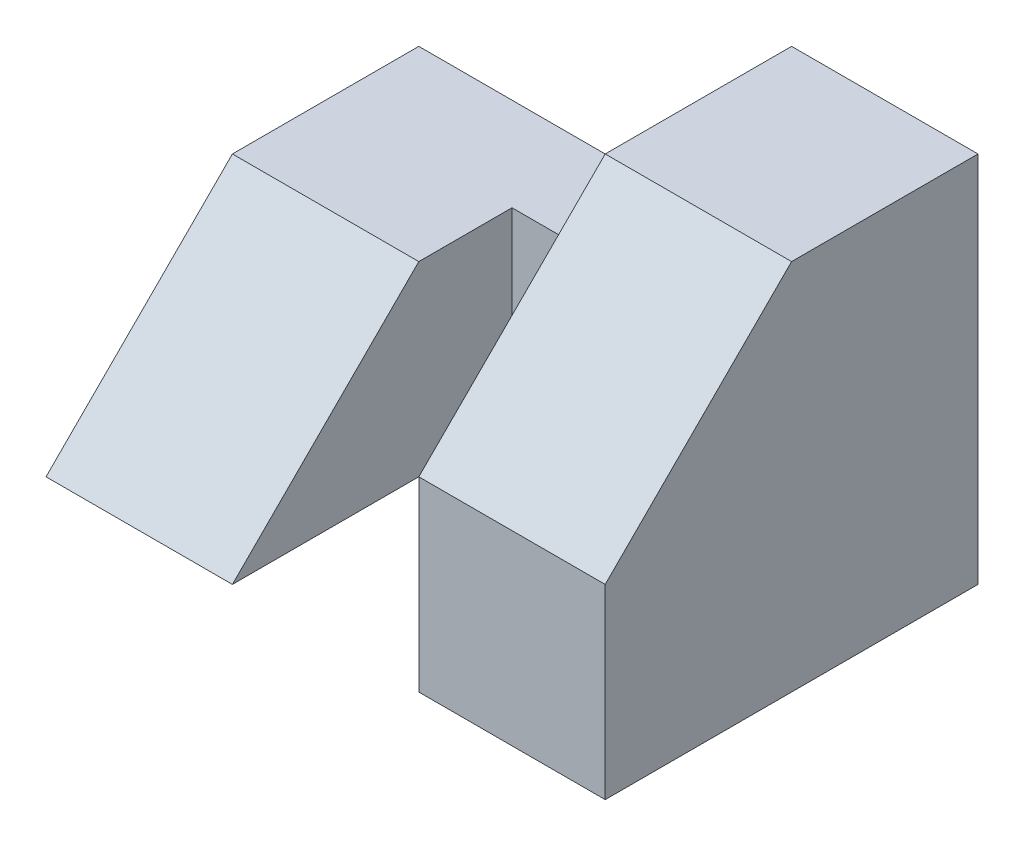
SolidWorks part; units mm, degrees
ref_plane "Front Plane" through (0, 0, 0) normal (0, 0, 1) x (1, 0, 0)
ref_plane "Top Plane" through (0, 0, 0) normal (0, 1, 0) x (1, 0, 0)
ref_plane "Right Plane" through (0, 0, 0) normal (1, 0, 0) x (0, 0, -1)
sketch "Sketch2" plane through (0, 0, 0) normal (0, 0, 1) x (1, 0, 0)
  line L1 (-76.2, -50.8) -> (76.2, -50.8)
  line L2 (-76.2, -50.8) -> (-76.2, 50.8)
  line L3 (-76.2, 50.8) -> (76.2, 50.8)
  line L4 (76.2, -50.8) -> (76.2, 50.8)
  line L5 (-76.2, -50.8) -> (76.2, 50.8) construction
  line L6 (-76.2, 50.8) -> (76.2, -50.8) construction
  point P0 (0, 0)
  dimension "D1" = 152.4
  dimension "D2" = 101.6
extrude "Boss-Extrude1" add sketch "Sketch2" along normal mid plane 101.6
sketch "Sketch4" plane through (0, 0, 50.8) normal (0, 0, 1) x (1, 0, 0)
  line L0 (76.2, -50.8) -> (76.2, 50.8) construction
  line L1 (-76.2, 50.8) -> (25.4, 50.8)
  line L2 (-76.2, 50.8) -> (-76.2, 0)
  line L3 (-76.2, 0) -> (25.4, 0)
  line L4 (25.4, 50.8) -> (25.4, 0)
  line L5 (-76.2, 50.8) -> (25.4, 0) construction
  line L6 (-76.2, 0) -> (25.4, 50.8) construction
  point P4 (-25.4, 25.4)
  dimension "D1" = 0
  dimension "D2" = 50.8
extrude "Cut-Extrude1" cut sketch "Sketch4" against normal through all
sketch "Sketch5" plane through (0, 0, 0) normal (0, 1, 0) x (1, 0, 0)
  line L0 (-76.2, 50.8) -> (25.4, 50.8) construction
  line L1 (25.4, -50.8) -> (-25.4, -50.8)
  line L2 (25.4, -50.8) -> (25.4, 25.4)
  line L3 (25.4, 25.4) -> (-25.4, 25.4)
  line L4 (-25.4, -50.8) -> (-25.4, 25.4)
  line L5 (25.4, -50.8) -> (-25.4, 25.4) construction
  line L6 (25.4, 25.4) -> (-25.4, -50.8) construction
  line L7 (-76.2, 50.8) -> (-76.2, -50.8) construction
  point P4 (0, -12.7)
  dimension "D1" = 25.4
  dimension "D2" = 50.8
extrude "Cut-Extrude2" cut sketch "Sketch5" against normal through all
chamfer "Chamfer1" distance 50.8 2 edges at (-50.8, 0, 50.8) (50.8, 50.8, 50.8)
